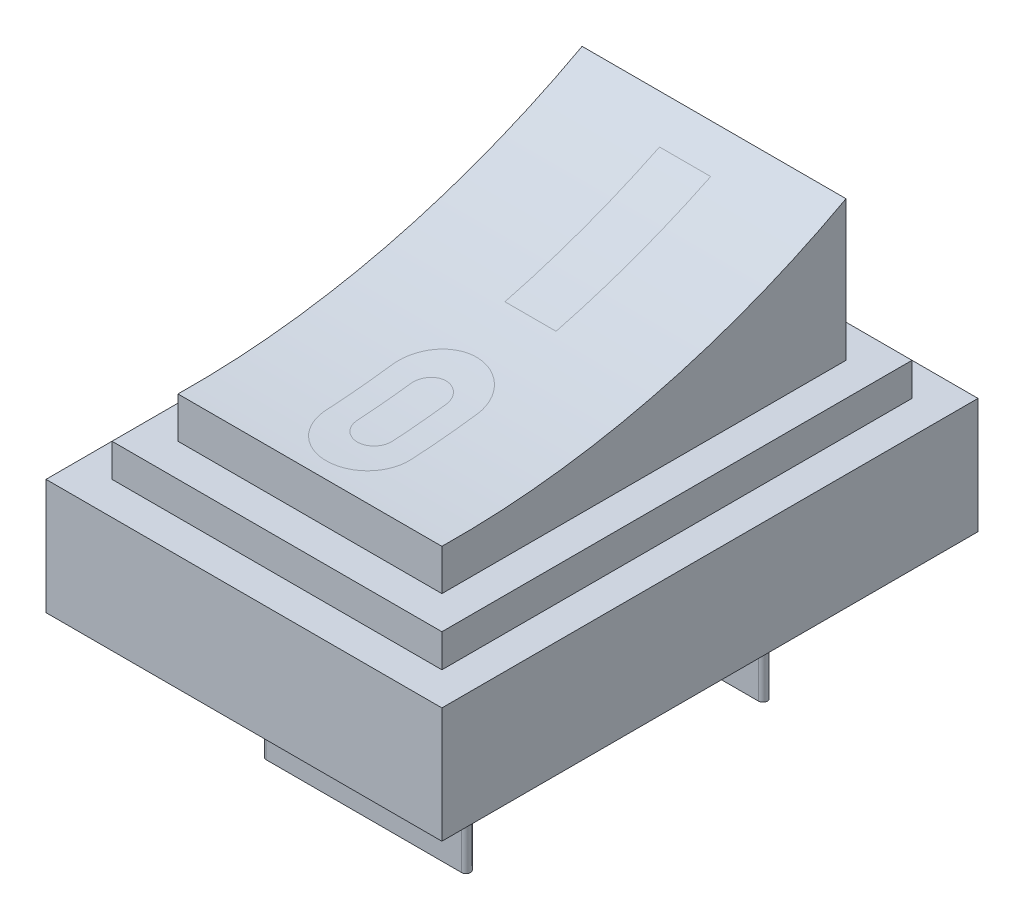
SolidWorks part; units mm, degrees
ref_plane "Front Plane" through (0, 0, 0) normal (0, 0, 1) x (1, 0, 0)
ref_plane "Top Plane" through (0, 0, 0) normal (0, 1, 0) x (1, 0, 0)
ref_plane "Right Plane" through (0, 0, 0) normal (1, 0, 0) x (0, 0, -1)
sketch "Sketch3" plane through (0, 0, 0) normal (1, 0, 0) x (0, 0, -1)
  line L1 (12.25, 0) -> (12.25, 3)
  line L2 (0, 0) -> (0, -1.2416)
  line L3 (0, -1.2416) -> (12.25, -1.2416)
  line L4 (12.25, -1.2416) -> (12.25, 0)
  arc A0 (12.25, 3) -> (0, 0) centre (0.3706, 24.9973) cw
  dimension "D3" = 25
  dimension "D1" = 3
  dimension "D2" = 12.25
extrude "Boss-Extrude1" add sketch "Sketch3" along normal mid plane 8
sketch "Sketch4" plane through (0, -1.2416, 0) normal (0, -1, 0) x (1, 0, 0)
  line L0 (4, 0) -> (-4, 0) construction
  line L1 (-5, 1) -> (5, 1)
  line L2 (-5, 1) -> (-5, -13.25)
  line L3 (-5, -13.25) -> (5, -13.25)
  line L4 (5, 1) -> (5, -13.25)
  line L5 (4, -12.25) -> (-4, -12.25) construction
  line L6 (4, 0) -> (4, -12.25) construction
  line L7 (-4, 0) -> (-4, -12.25) construction
  dimension "D1" = 1
  dimension "D2" = 1
  dimension "D3" = 1
  dimension "D4" = 1
extrude "Boss-Extrude3" add sketch "Sketch4" along normal blind 1
sketch "Sketch5" plane through (0, -2.2416, 0) normal (0, -1, 0) x (1, 0, 0)
  line L0 (5, 1) -> (-5, 1) construction
  line L1 (-6, 2) -> (6, 2)
  line L2 (-6, 2) -> (-6, -14.25)
  line L3 (-6, -14.25) -> (6, -14.25)
  line L4 (6, 2) -> (6, -14.25)
  line L5 (5, -13.25) -> (5, 1) construction
  line L6 (-5, 1) -> (-5, -13.25) construction
  line L7 (-5, -13.25) -> (5, -13.25) construction
  dimension "D1" = 1
  dimension "D2" = 1
  dimension "D3" = 1
  dimension "D4" = 1
extrude "Boss-Extrude4" add sketch "Sketch5" along normal blind 3.5
sketch "Sketch7" plane through (0, -5.7416, 0) normal (0, -1, 0) x (-1, 0, 0)
  line L0 (2.8035, 1.6091) -> (-3.1232, 1.6091) construction
  line L1 (-6, -2) -> (6, -2) construction
  line L2 (0, -2) -> (0, 14.25) construction
  line L3 (6, 14.25) -> (-6, 14.25) construction
  line L4 (2.8035, 1.4755) -> (-3.1232, 1.4755)
  line L5 (2.8035, 1.7428) -> (-3.1232, 1.7428)
  line L6 (2.8035, 10.6091) -> (-3.1232, 10.6091) construction
  line L7 (2.8035, 10.4755) -> (-3.1232, 10.4755)
  line L8 (2.8035, 10.7428) -> (-3.1232, 10.7428)
  arc A0 (2.8035, 1.4755) -> (2.8035, 1.7428) centre (2.8035, 1.6091) ccw
  arc A1 (-3.1232, 1.7428) -> (-3.1232, 1.4755) centre (-3.1232, 1.6091) ccw
  arc A2 (2.8035, 10.4755) -> (2.8035, 10.7428) centre (2.8035, 10.6091) ccw
  arc A3 (-3.1232, 10.7428) -> (-3.1232, 10.4755) centre (-3.1232, 10.6091) ccw
  point P8 (-0.1599, 1.6091)
  point P17 (-0.1599, 10.6091)
  dimension "D1" = 2
extrude "Boss-Extrude5" add sketch "Sketch7" along normal blind 4
sketch "Sketch9" plane through (0, 0, -10.7428) normal (0, 0, -1) x (-1, 0, 0)
  circle A0 centre (0, -7.7834) radius 0.75
extrude "Cut-Extrude1" cut sketch "Sketch9" against normal blind 15
sketch "Sketch13" plane through (0, -5.7416, 0) normal (0, -1, 0) x (1, 0, 0)
  line L0 (0, -1.7867) -> (0, -3.7867) construction
  line L1 (1.2925, -1.7867) -> (1.2925, -3.7867)
  line L2 (-1.2925, -1.7867) -> (-1.2925, -3.7867)
  line L3 (0, -1.9772) -> (0, -3.5987) construction
  line L4 (-0.6815, -6.6579) -> (0.8695, -6.6579)
  line L5 (-0.6815, -6.6579) -> (-0.6815, -11.6579)
  line L6 (-0.6815, -11.6579) -> (0.8695, -11.6579)
  line L7 (0.8695, -6.6579) -> (0.8695, -11.6579)
  line L8 (0.5405, -1.9772) -> (0.5405, -3.5987)
  line L9 (-0.5405, -1.9772) -> (-0.5405, -3.5987)
  arc A0 (1.2925, -1.7867) -> (-1.2925, -1.7867) centre (0, -1.7867) ccw
  arc A1 (-1.2925, -3.7867) -> (1.2925, -3.7867) centre (0, -3.7867) ccw
  arc A2 (0.5405, -1.9772) -> (-0.5405, -1.9772) centre (0, -1.9772) ccw
  arc A3 (-0.5405, -3.5987) -> (0.5405, -3.5987) centre (0, -3.5987) ccw
  point P3 (0, -2.7867)
  point P14 (0, -2.7879)
  dimension "D1" = 2
  dimension "D2" = 5
wrap "Wrap1" sketch "Sketch13" wrap type scribe source sketch "Sketch13" face at (0, 1.1074, -6.2211)
